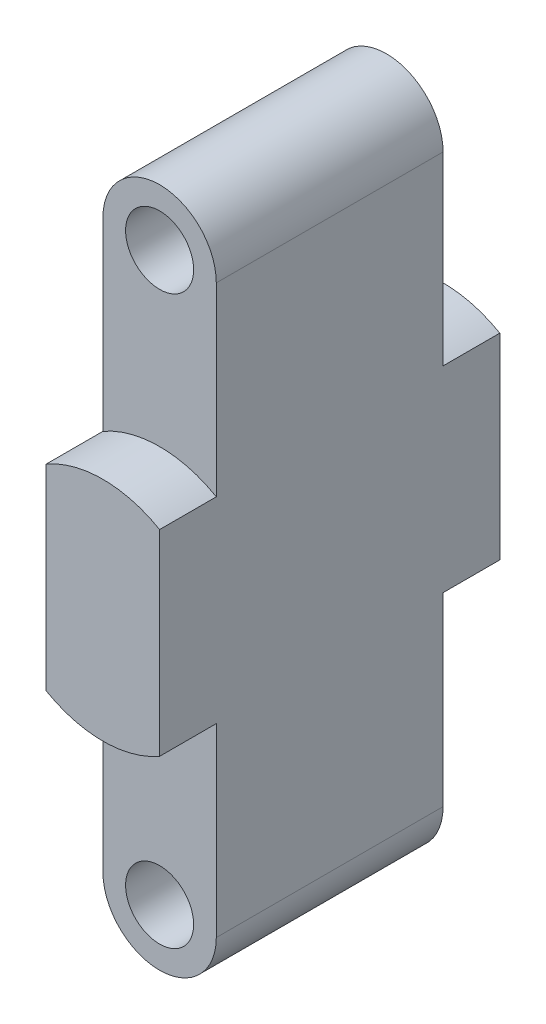
SolidWorks part; units mm, degrees
ref_plane "Front Plane" through (0, 0, 0) normal (0, 0, 1) x (1, 0, 0)
ref_plane "Top Plane" through (0, 0, 0) normal (0, 1, 0) x (1, 0, 0)
ref_plane "Right Plane" through (0, 0, 0) normal (1, 0, 0) x (0, 0, -1)
sketch "Sketch1" plane through (0, 0, 0) normal (0, 0, 1) x (1, 0, 0)
  line L1 (-6.35, 19.05) -> (6.35, 19.05)
  line L2 (-6.35, 19.05) -> (-6.35, -19.05)
  line L3 (-6.35, -19.05) -> (6.35, -19.05)
  line L4 (6.35, 19.05) -> (6.35, -19.05)
  line L5 (-6.35, 19.05) -> (6.35, -19.05) construction
  line L6 (-6.35, -19.05) -> (6.35, 19.05) construction
  point P0 (0, 0)
  dimension "D1" = 12.7
  dimension "D2" = 38.1
extrude "Boss-Extrude1" add sketch "Sketch1" along normal mid plane 38.1
fillet "Fillet2" 2 edges at (-6.35, -19.05, 0) (6.35, -19.05, 0) type full round first side face at (-6.35, 0, 0) second side face at (6.35, 0, 0) middle face at (0, -19.05, 0)
sketch "Sketch2" plane through (0, 0, 19.05) normal (0, 0, 1) x (1, 0, 0)
  circle A0 centre (0, -12.7) radius 3.81
  dimension "D1" = 7.62
extrude "Cut-Extrude1" cut sketch "Sketch2" against normal blind 38.1
sketch "Sketch8" plane through (0, 0, 19.05) normal (0, 0, 1) x (1, 0, 0)
  line L0 (-12.7, 19.05) -> (-12.7, -58.6125)
  line L1 (-12.7, -58.6125) -> (12.7, -58.6125)
  line L2 (12.7, -58.6125) -> (12.7, 19.05)
  arc A0 (-12.7, 19.05) -> (12.7, 19.05) centre (0, 19.05) ccw
  arc A1 (-6.35, -12.7) -> (6.35, -12.7) centre (0, -12.7) ccw construction
  point P5 (0, -19.05)
  dimension "D1" = 25.4
  dimension "D2" = 38.1
extrude "Cut-Extrude2" cut sketch "Sketch8" against normal blind 6.35
mirror "Mirror5" about plane through (0, 0, 0) normal (0, 0, 1) of "Cut-Extrude2"
mirror "Mirror7" about plane through (-6.35, 19.05, 19.05) normal (0, -1, 0) of "Mirror5", "Cut-Extrude2", "Cut-Extrude1", "Fillet2", "Boss-Extrude1"
